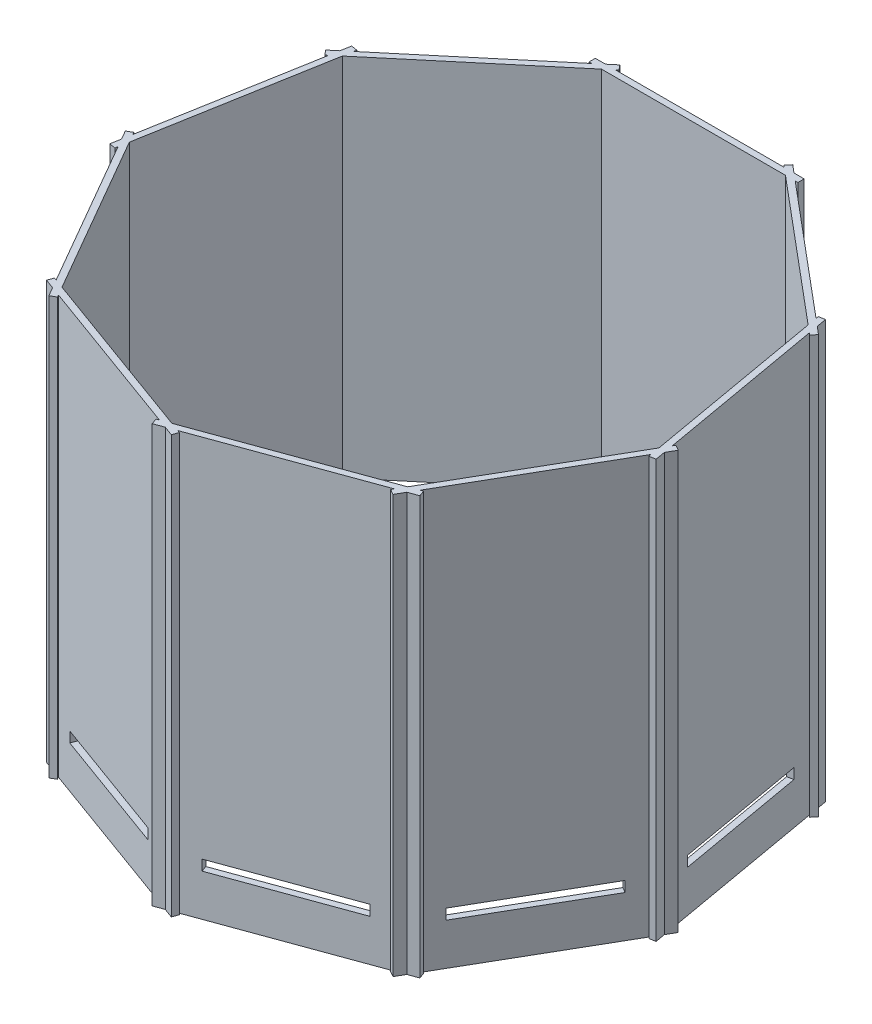
SolidWorks part; units mm, degrees
ref_plane "前基準面" through (0, 0, 0) normal (0, 0, 1) x (1, 0, 0)
ref_plane "上基準面" through (0, 0, 0) normal (0, 1, 0) x (1, 0, 0)
ref_plane "右基準面" through (0, 0, 0) normal (1, 0, 0) x (0, 0, -1)
sketch "草圖3" plane through (0, 0, 0) normal (0, 1, 0) x (1, 0, 0)
  line L0 (-8.497, 125) -> (6.4902, 125)
  line L1 (-50, 124) -> (50, 124)
  line L2 (-50, 124) -> (-50, 121)
  line L3 (-50, 121) -> (50, 121)
  line L4 (50, 124) -> (50, 121)
  circle A0 centre (0, 0) radius 125 construction
  point P8 (0, 124)
  dimension "D1" = 250
  dimension "D2" = 3
  dimension "D3" = 100
  dimension "D4" = 1
extrude "填料-伸長2" add sketch "草圖3" against normal blind 200 contours L1 L4 L3 L2
ref_plane "平面1" through (0, -180, 0) normal (0, -1, 0) x (-1, 0, 0)
sketch "草圖4" plane through (0, -180, 0) normal (0, -1, 0) x (-1, 0, 0)
  circle A0 centre (0, 0) radius 125
  dimension "D1" = 250
extrude "除料-伸長3" cut sketch "草圖4" against normal blind 5 contours A0
sketch "草圖5" plane through (0, 0, -121) normal (0, 0, 1) x (1, 0, 0)
  line L0 (-31.3688, -175) -> (-31.3688, -180) construction
  line L1 (-31.3688, -175) -> (31.3688, -175) construction
  line L2 (31.3688, -180) -> (31.3688, -175) construction
  line L3 (-31.3688, -180) -> (31.3688, -180) construction
  line L4 (-31.3688, -175) -> (-31.3688, -180)
  line L5 (-31.3688, -175) -> (31.3688, -175)
  line L6 (31.3688, -180) -> (31.3688, -175)
  line L7 (-31.3688, -180) -> (31.3688, -180)
extrude "除料-伸長4" cut sketch "草圖5" against normal through all
ref_axis "基準軸1" through (0, 0, 0) along (0, 1, 0)
pattern_circular "環狀複製排列1" count 9 every 40 about axis through (0, 0, 0) along (0, 1, 0) of "填料-伸長2", "除料-伸長4"
